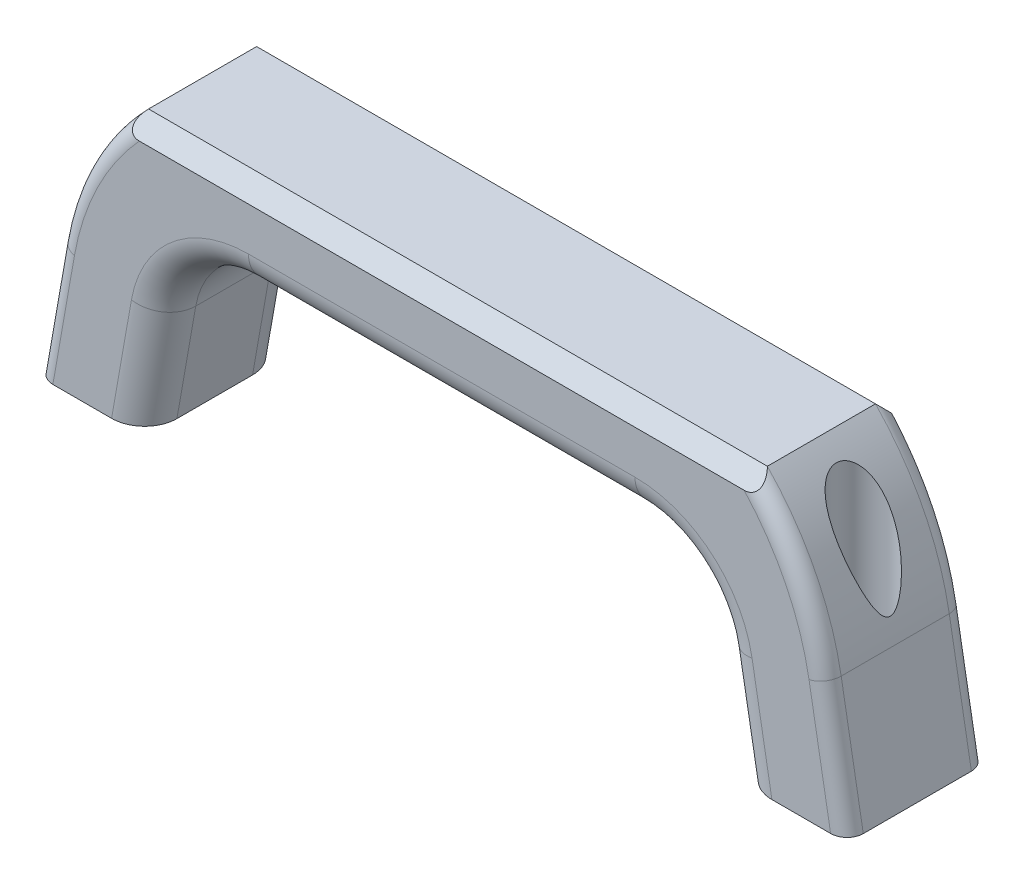
SolidWorks part; units mm, degrees
ref_plane "Front Plane" through (0, 0, 0) normal (0, 0, 1) x (1, 0, 0)
ref_plane "Top Plane" through (0, 0, 0) normal (0, 1, 0) x (1, 0, 0)
ref_plane "Right Plane" through (0, 0, 0) normal (1, 0, 0) x (0, 0, -1)
sketch "Sketch2" plane through (0, 0, 0) normal (0, 0, 1) x (1, 0, 0)
  line L0 (-55, 0) -> (-51.5125, 19.7784)
  line L1 (0, 33) -> (0, 0) construction
  line L3 (-35.7556, 33) -> (0, 33)
  line L5 (-55, 0) -> (-55, 33) construction
  line L6 (-75, 0) -> (-70.9095, 23.1986)
  line L7 (-57.2535, 50) -> (0, 50)
  line L8 (-55, 0) -> (-75, 0)
  line L10 (0, 50) -> (0, 33)
  line L11 (-57.2535, 50) -> (-55.3004, 52.0224) construction
  line L12 (-70.9095, 23.1986) -> (-51.5125, 19.7784) construction
  arc A0 (-51.5125, 19.7784) -> (-35.7556, 33) centre (-35.7556, 17) cw
  arc A1 (-70.9095, 23.1986) -> (-57.2535, 50) centre (-20.2497, 14.2659) cw
  point P2 (-65, 0)
  point P3 (-50.5066, 29.8336)
  dimension "D3" = 46
  dimension "D5" = 16
  dimension "D6" = 33
  dimension "D1" = 130
  dimension "D2" = 10
  dimension "D4" = 17
  dimension "D7" = 20
extrude "Boss-Extrude1" add sketch "Sketch2" along normal mid plane 26 contours A1 L7 L10 L3 A0 L0 L8 L6
fillet "Fillet1" radius 6 6 edges at (-17.8778, 33, -13) (-46.0402, 29.2567, -13) (-17.8778, 33, 13) (-46.0402, 29.2567, 13) (-53.2563, 9.8892, -13) (-53.2563, 9.8892, 13)
fillet "Fillet3" radius 3 4 edges at (-72.9547, 11.5993, -13) (-72.9547, 11.5993, 13) (-66.0842, 37.6197, -13) (-66.0842, 37.6197, 13)
sketch "Sketch6" plane through (0, 0, 0) normal (0, -1, 0) x (1, 0, 0)
  line L0 (-75, 0) -> (-55, 0) construction
  line L1 (-75, 10) -> (-75, -10) construction
  line L2 (-55, 7) -> (-55, -7) construction
  circle A0 centre (-65, 0) radius 3
  dimension "D1" = 6
extrude "Cut-Extrude3" cut sketch "Sketch6" against normal through all
sketch "Sketch7" plane through (0, 0, 0) normal (0, -1, 0) x (1, 0, 0)
  circle A0 centre (-65, 0) radius 5
  dimension "D1" = 10
extrude "Cut-Extrude4" cut sketch "Sketch7" against normal through all from offset 15 offset against normal yes
sketch "Sketch8" plane through (0, 15, 0) normal (0, 1, 0) x (1, 0, 0)
  line L0 (-68, 4) -> (-68, -4)
  line L1 (-62, 4) -> (-62, -4)
  circle A0 centre (-65, 0) radius 5 construction
  circle A1 centre (-65, 0) radius 5 construction
  arc A2 (-68, -4) -> (-62, -4) centre (-65, 0) ccw
  arc A3 (-68, 4) -> (-62, 4) centre (-65, 0) cw
  circle A4 centre (-65, 0) radius 3 construction
extrude "Cut-Extrude5" cut sketch "Sketch8" against normal blind 1
mirror "Mirror2" about plane through (0, 50, 13) normal (1, 0, 0) of bodies 110 101
sketch "Sketch3" plane through (0, 0, 0) normal (1, 0, 0) x (0, 0, -1)
  line L0 (-10, 50) -> (-13, 47)
  line L1 (-13, 47) -> (-13, 50)
  line L2 (-13, 50) -> (-10, 50)
  line L4 (-13, 50) -> (-13, 22.6776) construction
  point P2 (-13, 50)
  point P3 (-10, 50)
  point P5 (-13, 44)
extrude "Cut-Extrude1" cut sketch "Sketch3" against normal through all both and the other way through all
mirror "Mirror3" about plane through (0, 0, 0) normal (0, 0, 1) of "Cut-Extrude1"
sketch "Sketch9" plane through (0, 0, 0) normal (0, 0, 1) x (1, 0, 0)
  line L0 (-7.8467, 0) -> (-3.4512, 4.3955)
  line L1 (-3.4512, 4.3955) -> (5.8768, 4.3955)
  line L2 (5.8768, 4.3955) -> (10.2723, 0)
  line L3 (10.2723, 0) -> (-7.8467, 0)
  line L4 (1.2128, 4.3955) -> (1.2405, 9.0502)
  line L5 (-9.8799, -2.0703) -> (1.2405, -13.1907)
  line L6 (1.2405, -13.1907) -> (12.3609, -2.0703)
  line L7 (12.3609, -2.0703) -> (1.2405, 9.0502)
  line L8 (1.2405, 9.0502) -> (-9.8799, -2.0703)
  dimension "D1" = 4.3955
  dimension "D2" = 9.3279
  dimension "D3" = 4.6547
  dimension "D4" = 9.3279
